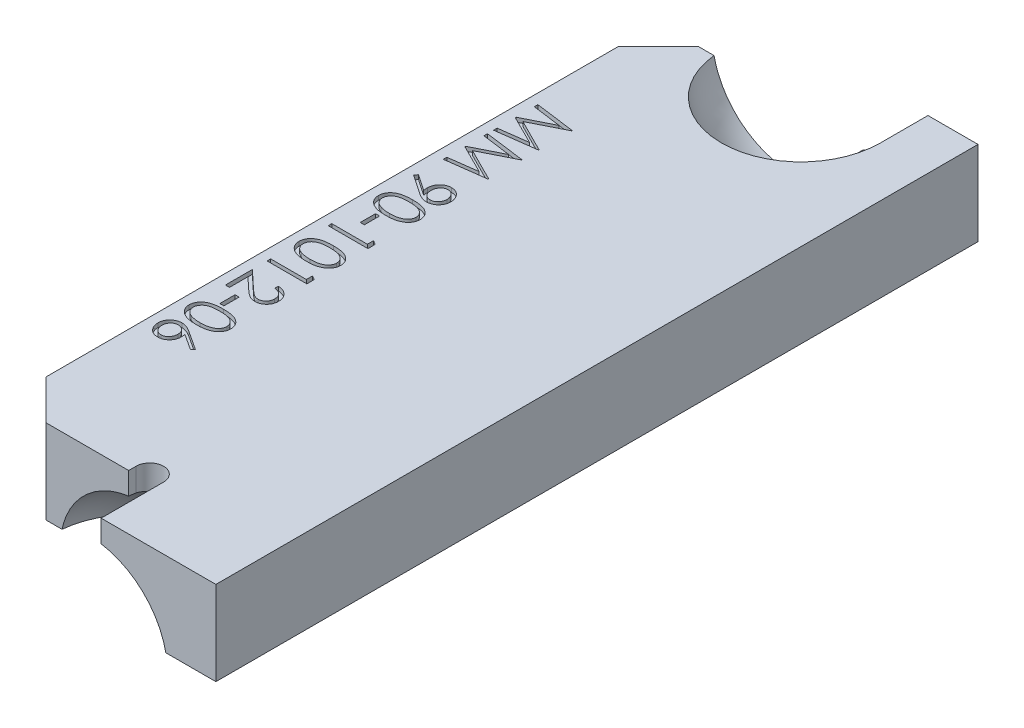
SolidWorks part; units mm, degrees
material "Acero M2"
ref_plane "Alzado" through (0, 0, 0) normal (0, 0, 1) x (1, 0, 0)
ref_plane "Planta" through (0, 0, 0) normal (0, 1, 0) x (1, 0, 0)
ref_plane "Vista lateral" through (0, 0, 0) normal (1, 0, 0) x (0, 0, -1)
sketch "Croquis1" plane through (0, 0, 0) normal (0, 1, 0) x (1, 0, 0)
  line L1 (0, 0) -> (-15.875, 0)
  line L2 (0, 0) -> (0, -45.72)
  line L3 (0, -45.72) -> (-15.875, -45.72)
  line L4 (-15.875, 0) -> (-15.875, -45.72)
  line L5 (-7.9375, -45.72) -> (-7.9375, 0) construction
  line L6 (0, -22.86) -> (-15.875, -22.86) construction
  point P180 (-7.9375, -22.86)
  dimension "D1" = 15.875
  dimension "D2" = 45.72
extrude "Saliente-Extruir1" add sketch "Croquis1" along normal blind 5.0546
sketch "Croquis2" plane through (0, 5.0546, 0) normal (0, 1, 0) x (1, 0, 0)
  line L0 (-7.7775, 0) -> (-7.7775, -2.8448) construction
  line L1 (-3.0023, 0) -> (-3.0023, -2.8448)
  line L2 (-12.5527, 0) -> (-12.5527, -2.8448)
  line L4 (-7.7775, -45.72) -> (-7.7775, -42.8752) construction
  line L5 (-12.5527, -45.72) -> (-12.5527, -42.8752) construction
  line L6 (-3.0023, -45.72) -> (-3.0023, -42.8752) construction
  line L7 (-7.7775, -2.8448) -> (-7.7775, -42.8752) construction
  line L8 (-7.7775, -22.86) -> (-15.875, -22.86) construction
  line L9 (-15.875, 0) -> (-15.875, -45.72) construction
  line L10 (-15.875, -45.72) -> (0, -45.72) construction
  line L11 (0, -45.72) -> (0, 0) construction
  arc A0 (-3.0023, 0) -> (-12.5527, 0) centre (-7.7775, 0) ccw
  arc A1 (-12.5527, -2.8448) -> (-3.0023, -2.8448) centre (-7.7775, -2.8448) ccw
  arc A2 (-12.5527, -45.72) -> (-3.0023, -45.72) centre (-7.7775, -45.72) ccw construction
  arc A3 (-3.0023, -42.8752) -> (-12.5527, -42.8752) centre (-7.7775, -42.8752) ccw construction
  point P2 (-7.7775, -1.4224)
  point P12 (-7.7775, -44.2976)
  dimension "D1" = 9.5504
  dimension "D2" = 42.8752
  dimension "D3" = 7.7775
extrude "Cortar-Extruir1" cut sketch "Croquis2" against normal offset from surface (3.7846 mm away) 1.27 up to face at (-7.9375, 0, 22.86)
sketch "Croquis6" plane through (0, 0, 0) normal (0, -1, 0) x (1, 0, 0)
  line L0 (-12.5527, 45.72) -> (-12.5527, 42.8752) construction
  line L1 (-3.0023, 45.72) -> (-3.0023, 42.8752) construction
  line L2 (-12.5527, 45.72) -> (-12.5527, 42.8752)
  line L3 (-3.0023, 45.72) -> (-3.0023, 42.8752)
  arc A0 (-12.5527, 42.8752) -> (-3.0023, 42.8752) centre (-7.7775, 42.8752) ccw construction
  arc A1 (-3.0023, 45.72) -> (-12.5527, 45.72) centre (-7.7775, 45.72) ccw construction
  arc A2 (-12.5527, 42.8752) -> (-3.0023, 42.8752) centre (-7.7775, 42.8752) ccw
  arc A3 (-3.0023, 45.72) -> (-12.5527, 45.72) centre (-7.7775, 45.72) ccw
extrude "Cortar-Extruir4" cut sketch "Croquis6" against normal offset from surface (3.7846 mm away) 1.27 up to face at (-7.8575, 5.0546, 12.7381)
fillet "Redondeo1" radius 4.7625 6 edges at (-12.5527, 1.27, 1.4224) (-3.0023, 1.27, 1.4224) (-7.7775, 1.27, 7.62) (-3.0023, 3.7846, 44.2976) (-12.5527, 3.7846, 44.2976) (-7.7775, 3.7846, 38.1)
sketch "Croquis4" plane through (0, 5.0546, 0) normal (0, 1, 0) x (1, 0, 0)
  line L0 (0, -45.72) -> (0, 0) construction
  line L1 (-15.875, 0) -> (-6.8834, 0)
  line L2 (-15.875, 0) -> (-15.875, -3.302)
  line L3 (-15.875, -3.302) -> (-6.8834, -3.302)
  line L4 (-6.8834, 0) -> (-6.8834, -3.302)
  line L5 (-11.3792, -3.302) -> (-11.3792, 0) construction
  line L6 (-15.875, -1.651) -> (-6.8834, -1.651) construction
  line L7 (-15.875, -45.72) -> (-6.8834, -45.72)
  line L8 (-15.875, -45.72) -> (-15.875, -42.418)
  line L9 (-15.875, -42.418) -> (-6.8834, -42.418)
  line L10 (-6.8834, -45.72) -> (-6.8834, -42.418)
  line L11 (-11.3792, -42.418) -> (-11.3792, -45.72) construction
  line L12 (-15.875, -44.069) -> (-6.8834, -44.069) construction
  point P68 (-11.3792, -1.651)
  point P102 (-11.3792, -44.069)
  dimension "D1" = 39.116
  dimension "D2" = 6.8834
extrude "Cortar-Extruir2" cut sketch "Croquis4" against normal through all
sketch "Croquis5" plane through (0, 5.0546, 0) normal (0, 1, 0) x (1, 0, 0)
  line L0 (-7.7089, 0) -> (-7.7089, -3.7465) construction
  line L1 (-6.8834, 0) -> (-6.8834, -3.7465)
  line L2 (-8.5344, 0) -> (-8.5344, -3.7465)
  line L3 (-7.7089, -45.72) -> (-7.7089, -41.9735) construction
  line L4 (-8.5344, -45.72) -> (-8.5344, -41.9735)
  line L5 (-6.8834, -45.72) -> (-6.8834, -41.9735)
  line L6 (-6.8834, -45.72) -> (-6.8834, -42.418) construction
  line L8 (-6.8834, -45.72) -> (0, -45.72) construction
  line L10 (-6.8834, 0) -> (-6.8834, -2.8448) construction
  line L11 (-3.0023, 0) -> (-6.8834, 0) construction
  arc A0 (-6.8834, 0) -> (-8.5344, 0) centre (-7.7089, 0) ccw
  arc A1 (-8.5344, -3.7465) -> (-6.8834, -3.7465) centre (-7.7089, -3.7465) ccw
  arc A2 (-8.5344, -45.72) -> (-6.8834, -45.72) centre (-7.7089, -45.72) ccw
  arc A3 (-6.8834, -41.9735) -> (-8.5344, -41.9735) centre (-7.7089, -41.9735) ccw
  point P2 (-7.7089, -1.8732)
  point P7 (-7.7089, -43.8468)
  dimension "D1" = 0.8255
  dimension "D2" = 38.227
extrude "Cortar-Extruir3" cut sketch "Croquis5" against normal through all
chamfer "Chaflán1" distance 2.3813 angle 45 2 edges at (-15.875, 2.5273, 3.302) (-15.875, 2.5273, 42.418)
sketch "Croquis11" plane through (0, 5.0546, 0) normal (0, 1, 0) x (1, 0, 0)
  line L0 (-15.2672, -3.9098) -> (-15.2672, -41.8102) construction
  line L1 (-15.2672, -22.86) -> (-15.875, -22.86) construction
  line L2 (-15.875, -5.6833) -> (-15.875, -40.0367) construction
  text T0 "MM 90-1012-06" font "Century Gothic" height 2.3813
extrude "Cortar-Extruir9" cut sketch "Croquis11" against normal blind 0.254
